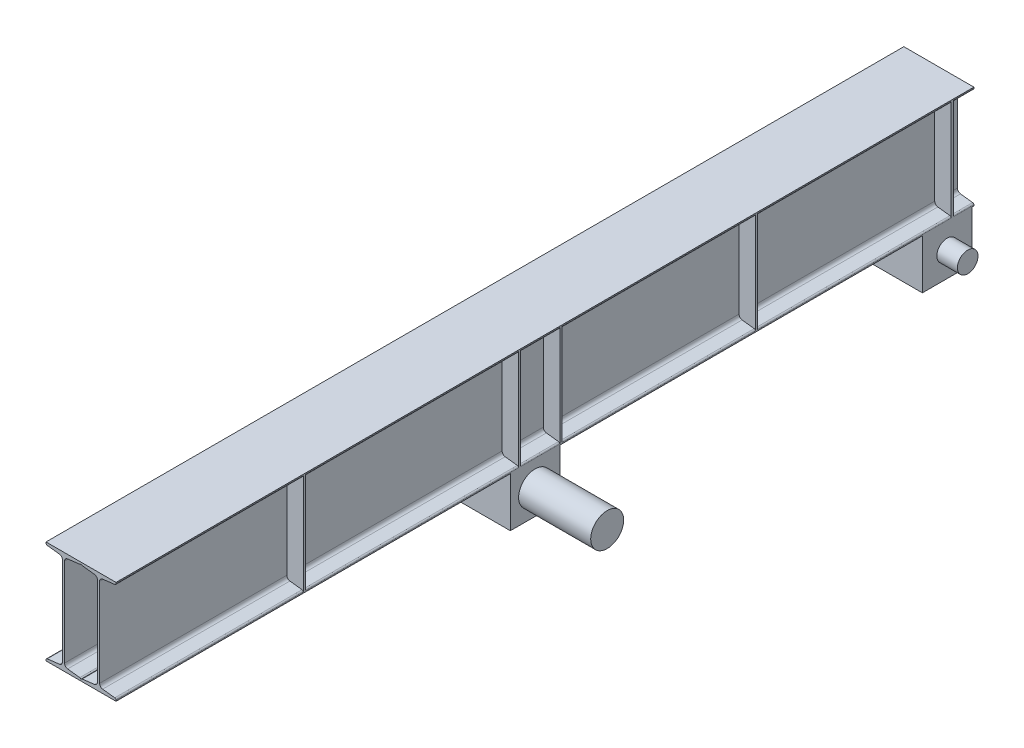
SolidWorks part; units mm, degrees
ref_plane "Плоскость1" through (0, 0, 0) normal (0, 0, 1) x (1, 0, 0)
ref_plane "Плоскость2" through (0, 0, 0) normal (0, 1, 0) x (1, 0, 0)
ref_plane "Плоскость3" through (0, 0, 0) normal (1, 0, 0) x (0, 0, -1)
sketch "Двотавр профіль" plane through (0, 0, 0) normal (0, 0, 1) x (1, 0, 0)
  line L0 (0, 0) -> (0, -21.6801) construction
  line L2 (5, 464.3728) -> (5, 35.6272)
  line L3 (19.9649, 18.7494) -> (78.838, 11.6506)
  line L4 (85, 4.7009) -> (85, 0)
  line L5 (85, 0) -> (-85, 0)
  line L7 (-85, 4.7009) -> (-85, 0)
  line L8 (-19.9649, 18.7494) -> (-78.838, 11.6506)
  line L9 (-5, 464.3728) -> (-5, 35.6272)
  line L11 (-19.9649, 481.2506) -> (-78.838, 488.3494)
  line L12 (-85, 495.2991) -> (-85, 500)
  line L13 (85, 500) -> (-85, 500)
  line L14 (85, 495.2991) -> (85, 500)
  line L15 (19.9649, 481.2506) -> (78.838, 488.3494)
  arc A0 (85, 4.7009) -> (78.838, 11.6506) centre (78, 4.7009) ccw
  arc A1 (-19.9649, 18.7494) -> (-5, 35.6272) centre (-22, 35.6272) ccw
  arc A2 (19.9649, 18.7494) -> (5, 35.6272) centre (22, 35.6272) cw
  arc A3 (-85, 4.7009) -> (-78.838, 11.6506) centre (-78, 4.7009) cw
  arc A4 (-85, 495.2991) -> (-78.838, 488.3494) centre (-78, 495.2991) ccw
  arc A5 (19.9649, 481.2506) -> (5, 464.3728) centre (22, 464.3728) ccw
  arc A6 (-19.9649, 481.2506) -> (-5, 464.3728) centre (-22, 464.3728) cw
  arc A7 (85, 495.2991) -> (78.838, 488.3494) centre (78, 495.2991) cw
  point P10 (49.4014, 15.2)
  dimension "Зовнішній радіус" = 7
  dimension "Внутрішній радіус" = 17
  dimension "Товщина середини основи" = 15.2
  dimension "Товщина стінки" = 10
  dimension "Кут основи" = 6.875
  dimension "Ширина" = 170
  dimension "Висота" = 500
extrude "Двотавр" add sketch "Двотавр профіль" along normal blind 4164
sketch "Ребро профіль" plane through (85, 0, 0) normal (1, 0, 0) x (0, 0, -1)
  line L0 (-4164, 4.7009) -> (0, 4.7009) construction
  line L1 (-100, 4.7009) -> (-110, 4.7009)
  line L2 (-100, 4.7009) -> (-100, 495.2991)
  line L3 (-100, 495.2991) -> (-110, 495.2991)
  line L4 (-110, 4.7009) -> (-110, 495.2991)
  line L5 (-4164, 495.2991) -> (0, 495.2991) construction
  line L6 (0, 35.6272) -> (0, 464.3728) construction
  dimension "Товщина" = 10
  dimension "Координата" = 100
extrude "Ребро1" add sketch "Ребро профіль" against normal up to surface (80 mm away) up to face at (5, 250, 2082)
pattern_linear "Масив ребер1" count 3 along (0, 0, 1) of "Ребро1"
pattern_linear "Масив ребер2" count 2 along (0, 0, 1) of "Ребро1"
pattern_linear "Масив ребер3" count 2 along (0, 0, 1) of "Ребро1"
sketch "Профіль опори балансира" plane through (0, 0, 0) normal (0, -1, 0) x (1, 0, 0)
  line L0 (85, 4164) -> (85, 0) construction
  line L1 (85, 2010) -> (-85, 2010)
  line L2 (85, 2010) -> (85, 2250)
  line L3 (85, 2250) -> (-85, 2250)
  line L4 (-85, 2010) -> (-85, 2250)
  line L5 (-85, 4164) -> (-85, 0) construction
  line L6 (-85, 0) -> (85, 0) construction
  dimension "Координата" = 2010
  dimension "Ширина" = 240
extrude "Опора балансира" add sketch "Профіль опори балансира" along normal blind 240
sketch "Профіль вала опори балансира" plane through (85, 0, 0) normal (1, 0, 0) x (0, 0, -1)
  line L0 (-2250, -240) -> (-2250, 0) construction
  line L1 (-2010, -240) -> (-2250, -240) construction
  line L2 (-2250, -120) -> (-2010, -120) construction
  line L3 (-2010, -240) -> (-2010, 0) construction
  circle A0 centre (-2130, -120) radius 80
  dimension "Діаметр" = 160
  dimension "Висота центра" = 120
extrude "Вал опори балансира" add sketch "Профіль вала опори балансира" along normal blind 350
sketch "Профіль опори" plane through (0, 0, 0) normal (0, -1, 0) x (1, 0, 0)
  line L0 (-85, 4164) -> (-85, 2250) construction
  line L1 (-85, 250) -> (85, 250)
  line L2 (-85, 250) -> (-85, 10)
  line L3 (-85, 10) -> (85, 10)
  line L4 (85, 250) -> (85, 10)
  line L5 (85, 4164) -> (85, 2250) construction
  line L7 (-85, 0) -> (85, 0) construction
  dimension "Ширина" = 240
  dimension "Координата" = 10
extrude "Опора" add sketch "Профіль опори" along normal blind 240
sketch "Профіль вала опори" plane through (85, 0, 0) normal (1, 0, 0) x (0, 0, -1)
  line L0 (-250, -240) -> (-250, 0) construction
  line L1 (-10, -240) -> (-250, -240) construction
  line L2 (-250, -120) -> (-10, -120) construction
  line L3 (-10, -240) -> (-10, 0) construction
  circle A0 centre (-130, -120) radius 50
  dimension "Діаметр" = 100
  dimension "Висота центра" = 120
extrude "Вал опори" add sketch "Профіль вала опори" along normal blind 100
mirror "Дзеркальне відображення" about plane through (-85, 4.7009, 4164) normal (1, 0, 0) of "Вал опори", "Опора", "Двотавр", "Ребро1", "Масив ребер1", "Масив ребер2", "Масив ребер3", "Опора балансира", "Вал опори балансира"
equation "\"Зовнішній радіус@Двотавр профіль\" = 7.0"
equation "\"Внутрішній радіус@Двотавр профіль\" = 17.0"
equation "\"Товщина середини основи@Двотавр профіль\" = 15.2"
equation "\"Товщина стінки@Двотавр профіль\" = 10.0"
equation "\"Кут основи@Двотавр профіль\" = 0.12"
equation "\"Ширина@Двотавр профіль\" = 170.0"
equation "\"Висота@Двотавр профіль\" = 500.0"
equation "\"Довжина@Двотавр\" = 4164.0"
equation "\"Товщина@Ребро профіль\" = 10.0"
equation "\"Координата@Ребро профіль\" = 100.0"
equation "\"Координата@Масив ребер1\" = 950.0"
equation "\"D1@Масив ребер1\" = 3"
equation "\"Координата@Масив ребер2\" = 2100.0"
equation "\"D1@Масив ребер2\" = 2"
equation "\"Координата@Масив ребер3\" = 3145.0"
equation "\"D1@Масив ребер3\" = 2"
equation "\"Координата@Профіль опори балансира\" = 2010.0"
equation "\"Ширина@Профіль опори балансира\" = 240.0"
equation "\"Висота@Опора балансира\" = 240.0"
equation "\"Висота центра@Профіль вала опори балансира\" = 120.0"
equation "\"Діаметр@Профіль вала опори балансира\" = 160.0"
equation "\"Довжина@Вал опори балансира\" = 350.0"
equation "\"Ширина@Профіль опори\" = 240.0"
equation "\"Координата@Профіль опори\" = 10.0"
equation "\"Висота@Опора\" = 240.0"
equation "\"Висота центра@Профіль вала опори\" = 120.0"
equation "\"Діаметр@Профіль вала опори\" = 100.0"
equation "\"Довжина@Вал опори\" = 100.0"
